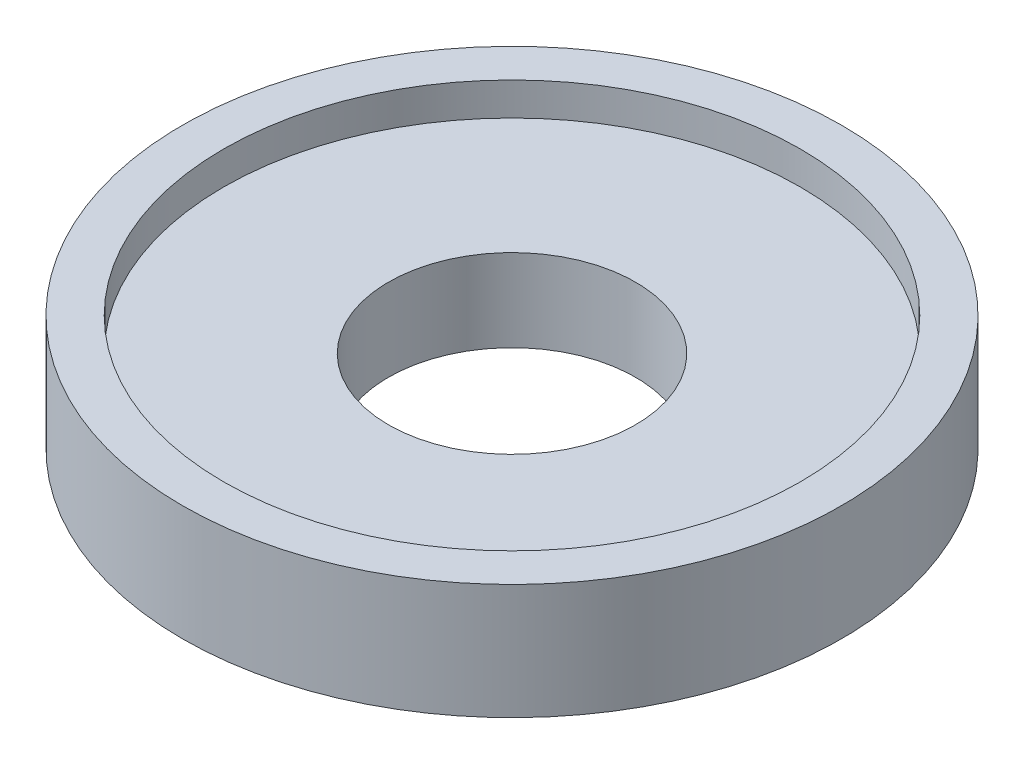
SolidWorks part; units mm, degrees
ref_plane "Front Plane" through (0, 0, 0) normal (0, 0, 1) x (1, 0, 0)
ref_plane "Top Plane" through (0, 0, 0) normal (0, 1, 0) x (1, 0, 0)
ref_plane "Right Plane" through (0, 0, 0) normal (1, 0, 0) x (0, 0, -1)
sketch "Sketch1" plane through (0, 0, 0) normal (0, 1, 0) x (1, 0, 0)
  circle A0 centre (0, 0) radius 20
  circle A1 centre (0, 0) radius 17.5
  dimension "D1" = 40
  dimension "D2" = 35
extrude "Boss-Extrude1" add sketch "Sketch1" along normal blind 5 contours A0 A1 | A1
sketch "Sketch2" plane through (0, 0, 0) normal (0, 1, 0) x (1, 0, 0)
  line L1 (7.5, -7.5) -> (-7.5, -7.5)
  line L2 (7.5, -7.5) -> (7.5, 7.5)
  line L3 (7.5, 7.5) -> (-7.5, 7.5)
  line L4 (-7.5, -7.5) -> (-7.5, 7.5)
  line L5 (7.5, -7.5) -> (-7.5, 7.5) construction
  line L6 (7.5, 7.5) -> (-7.5, -7.5) construction
  dimension "D1" = 7.5
  dimension "D2" = 15
  dimension "D3" = 15
  dimension "D4" = 7.5
extrude "Cut-Extrude1" [suppressed] cut sketch "Sketch2" along normal blind 15 contours L4 L3 L2 L1
extrude "Boss-Extrude3" add sketch "Sketch1<3>" along normal blind 7
sketch "Sketch1<3>" plane through (0, 0, 0) normal (0, 1, 0) x (1, 0, 0) same geometry as "Sketch1"
sketch "Sketch3" plane through (0, 5, 0) normal (0, 1, 0) x (1, 0, 0)
  circle A0 centre (0, 0) radius 7.5
  dimension "D1" = 15
extrude "Cut-Extrude2" cut sketch "Sketch3" against normal blind 7
chamfer "Chamfer1" [suppressed] distance 1 angle 45
